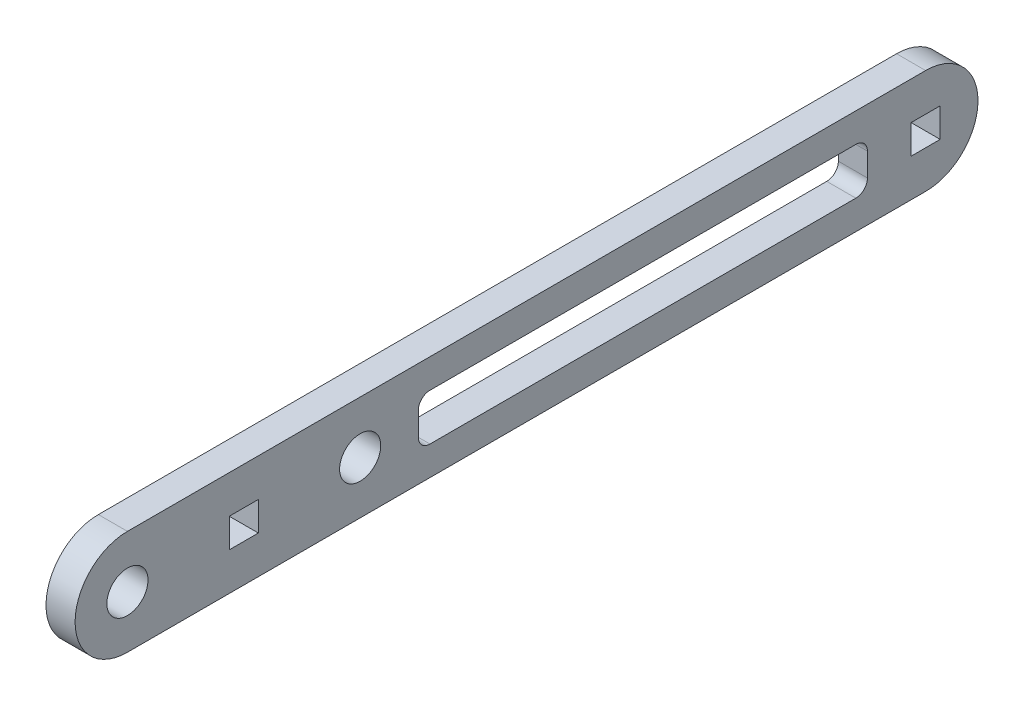
SolidWorks part; units mm, degrees
material "Custom Plastic"
ref_plane "Front Plane" through (0, 0, 0) normal (0, 0, 1) x (1, 0, 0)
ref_plane "Top Plane" through (0, 0, 0) normal (0, 1, 0) x (1, 0, 0)
ref_plane "Right Plane" through (0, 0, 0) normal (1, 0, 0) x (0, 0, -1)
sketch "Sketch1" plane through (0, 0, 0) normal (1, 0, 0) x (0, 0, -1)
  line L0 (0, 0) -> (-74.422, 0) construction
  line L1 (-88.7095, -1.5875) -> (-85.5345, 1.5875) construction
  line L2 (-72.8345, -1.5875) -> (-76.0095, -1.5875)
  line L3 (-72.8345, -1.5875) -> (-72.8345, 1.5875)
  line L4 (-72.8345, 1.5875) -> (-76.0095, 1.5875)
  line L5 (-76.0095, -1.5875) -> (-76.0095, 1.5875)
  line L6 (-72.8345, -1.5875) -> (-76.0095, 1.5875) construction
  line L7 (-72.8345, 1.5875) -> (-76.0095, -1.5875) construction
  line L8 (-63.3095, -1.5875) -> (-60.1345, 1.5875) construction
  line L9 (-87.122, 0) -> (-74.422, 0) construction
  line L10 (-87.122, 5.715) -> (0, 5.715)
  line L11 (-87.122, 5.715) -> (-87.122, 0) construction
  line L12 (0, -5.715) -> (-87.122, -5.715)
  line L13 (-87.122, 0) -> (-87.122, -5.715) construction
  line L14 (-55.372, 0) -> (-55.372, 1.27)
  line L15 (-54.102, 2.54) -> (-7.62, 2.54)
  line L16 (-6.35, 1.27) -> (-6.35, -1.27)
  line L17 (-7.62, -2.54) -> (-54.102, -2.54)
  line L18 (-55.372, -1.27) -> (-55.372, 0)
  line L20 (1.5875, -1.5875) -> (-1.5875, -1.5875)
  line L21 (1.5875, -1.5875) -> (1.5875, 1.5875)
  line L22 (1.5875, 1.5875) -> (-1.5875, 1.5875)
  line L23 (-1.5875, -1.5875) -> (-1.5875, 1.5875)
  line L24 (1.5875, -1.5875) -> (-1.5875, 1.5875) construction
  line L25 (1.5875, 1.5875) -> (-1.5875, -1.5875) construction
  circle A0 centre (-61.722, 0) radius 2.2451
  circle A1 centre (-87.122, 0) radius 2.2451
  circle A2 centre (0, 0) radius 2.2451 construction
  arc A3 (-87.122, 5.715) -> (-87.122, -5.715) centre (-87.122, 0) ccw
  arc A4 (0, 5.715) -> (0, -5.715) centre (0, 0) cw
  arc A5 (-7.62, 2.54) -> (-6.35, 1.27) centre (-7.62, 1.27) cw
  arc A6 (-6.35, -1.27) -> (-7.62, -2.54) centre (-7.62, -1.27) cw
  arc A7 (-54.102, -2.54) -> (-55.372, -1.27) centre (-54.102, -1.27) cw
  arc A8 (-55.372, 1.27) -> (-54.102, 2.54) centre (-54.102, 1.27) cw
  circle A9 centre (-74.422, 0) radius 2.2451 construction
  dimension "D5" = 5.715
  dimension "D9" = 1.27
  dimension "D1" = 74.422
  dimension "D2" = 3.175
  dimension "D3" = 12.7
  dimension "D4" = 12.7
  dimension "D6" = 6.35
  dimension "D7" = 6.35
  dimension "D8" = 3.175
extrude "Boss-Extrude1" add sketch "Sketch1" along normal blind 3.175
